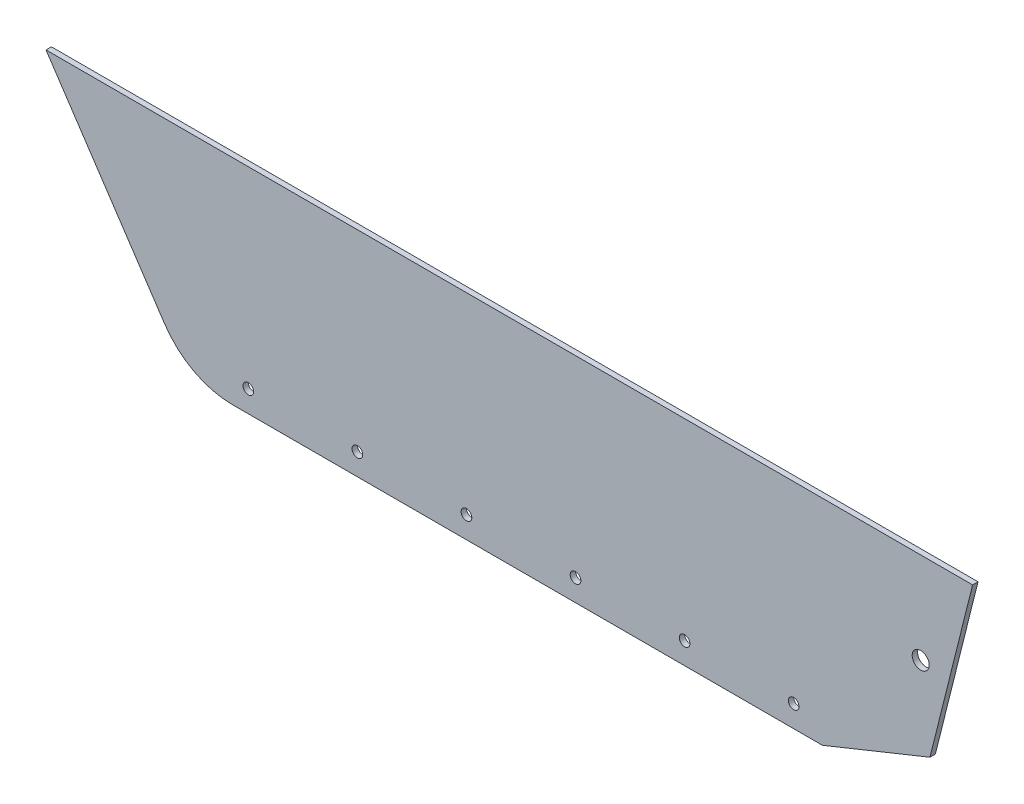
SolidWorks part; units mm, degrees
material "5052-H34"
ref_plane "Front Plane" through (0, 0, 0) normal (0, 0, 1) x (1, 0, 0)
ref_plane "Top Plane" through (0, 0, 0) normal (0, 1, 0) x (1, 0, 0)
ref_plane "Right Plane" through (0, 0, 0) normal (1, 0, 0) x (0, 0, -1)
sketch "Sketch1" plane through (0, 0, 0) normal (0, 0, 1) x (1, 0, 0)
  line L6 (-98.8794, 3.851) -> (-31.8794, -96.649)
  line L7 (428.1206, 28.9396) -> (403.1206, -71.149)
  line L9 (403.1206, -71.149) -> (366, -96.649)
  line L10 (-31.8794, -96.649) -> (366, -96.649)
  line L12 (-98.8794, 3.851) -> (-115.6052, 28.9396)
  line L13 (-115.6052, 28.9396) -> (428.1206, 28.9396)
  circle A0 centre (3.1206, -83.899) radius 3.125
  circle A1 centre (67.1206, -83.899) radius 3.125
  circle A2 centre (131.1206, -83.899) radius 3.125
  circle A3 centre (195.1206, -83.899) radius 3.125
  circle A4 centre (259.1206, -83.899) radius 3.125
  circle A5 centre (323.1206, -83.899) radius 3.125
  point P0 (-48.8794, -71.149)
  point P2 (-31.8794, -96.649)
  point P8 (48, -83.899)
  point P9 (403.1206, -71.149)
  dimension "D2" = 64
  dimension "D4" = 64
  dimension "D14" = 6.25
  dimension "D1" = 25.5
  dimension "D3" = 75
  dimension "D5" = 25
  dimension "D6" = 80
  dimension "D7" = 527
  dimension "D8" = 180
  dimension "D9" = 64
  dimension "D10" = 64
  dimension "D11" = 64
  dimension "D12" = 123.69
  dimension "D13" = 12.75
  dimension "D15" = 366
  dimension "D16" = 115.6052
extrude "Boss-Extrude1" add sketch "Sketch1" along normal blind 3.175 contours L12 L13 L7 L9 L10 L6
extrude "Cut-Extrude1" cut sketch "Sketch1<4>" along normal through all contours A0 | A1 | A2 | A3 | A4 | A5 region at (3.1206, -83.899, 0)
sketch "Sketch1<4>" plane through (0, 0, 0) normal (0, 0, 1) x (1, 0, 0) same geometry as "Sketch1"
sketch "Sketch2" plane through (0, 0, 0) normal (0, 0, -1) x (-1, 0, 0)
  circle A0 centre (-291.1206, -83.899) radius 6.5
  circle A2 centre (-241.5603, -124.3932) radius 6.5
  circle A3 centre (-192, -83.899) radius 6.5
  circle A4 centre (-128, -83.899) radius 6.5
  circle A5 centre (-64, -83.899) radius 6.5
  circle A6 centre (0, -83.899) radius 6.5
  dimension "D2" = 0
  dimension "D3" = 64
  dimension "D4" = 64
  dimension "D5" = 64
  dimension "D6" = 64
  dimension "D7" = 64
  dimension "D8" = 13
  dimension "D1" = 32
sketch "Sketch5" plane through (0, 0, 0) normal (0, 0, -1) x (-1, 0, 0)
  line L0 (48.8794, -71.149) -> (-14.2353, -96.649)
  line L1 (31.8794, -96.649) -> (-366, -96.649) construction
  line L2 (-14.2353, -96.649) -> (31.8794, -96.649)
  line L3 (31.8794, -96.649) -> (48.8794, -71.149)
  line L6 (-366, -96.649) -> (-403.1206, -71.149)
  line L7 (-403.1206, -71.149) -> (-352, -71.149)
  line L9 (-352, -71.149) -> (-326.5, -96.649)
  line L11 (-366, -96.649) -> (-326.5, -96.649)
  dimension "D1" = 22
  dimension "D2" = 45
extrude "Cut-Extrude2" [suppressed] cut sketch "Sketch5" against normal up to next
sketch "Sketch6" plane through (0, 0, 3.175) normal (0, 0, 1) x (1, 0, 0)
  line L0 (-48.8794, -71.149) -> (14.2353, -96.649)
  line L1 (-31.8794, -96.649) -> (366, -96.649) construction
  line L2 (14.2353, -96.649) -> (-31.8794, -96.649)
  line L3 (-31.8794, -96.649) -> (-48.8794, -71.149)
  dimension "D1" = 158
fillet "Fillet1" radius 48 1 edges at (-31.8794, -96.649, 1.5875)
sketch "Sketch7" plane through (0, 0, 3.175) normal (0, 0, 1) x (1, 0, 0)
  line L0 (403.1206, -71.149) -> (340.0059, -96.649)
  line L1 (-31.8794, -96.649) -> (366, -96.649) construction
  line L2 (340.0059, -96.649) -> (366, -96.649)
  line L3 (366, -96.649) -> (403.1206, -71.149)
  dimension "D1" = 22
extrude "Cut-Extrude3" cut sketch "Sketch7" against normal blind 10
sketch "Sketch9" plane through (0, 0, 0) normal (0, 0, -1) x (-1, 0, 0)
  line L0 (-403.1206, -71.149) -> (48.8794, -71.149)
  line L1 (48.8794, -71.149) -> (48.8794, -114.9143)
  line L2 (48.8794, -114.9143) -> (-403.1206, -114.9143)
  line L3 (-403.1206, -114.9143) -> (-403.1206, -71.149)
sketch "Sketch11" plane through (0, 0, 0) normal (0, 0, -1) x (-1, 0, 0)
  circle A0 centre (-397.6786, -24.6104) radius 5
extrude "Cut-Extrude5" cut sketch "Sketch11" against normal up to next
sketch "Sketch12" plane through (0, 0, 3.175) normal (0, 0, 1) x (1, 0, 0)
  line L1 (875.2623, -24.6104) -> (-79.9052, -24.6104)
  line L2 (-115.6052, 28.9396) -> (-46.129, -75.2746) construction
  line L3 (-6.1906, -96.649) -> (340.0059, -96.649) construction
  circle A0 centre (397.6786, -24.6104) radius 5 construction
  circle A1 centre (397.6786, -24.6104) radius 5
  point P8 (397.6786, -24.6104)
  point P10 (-64.9052, -24.6104)
  dimension "D1" = 15
